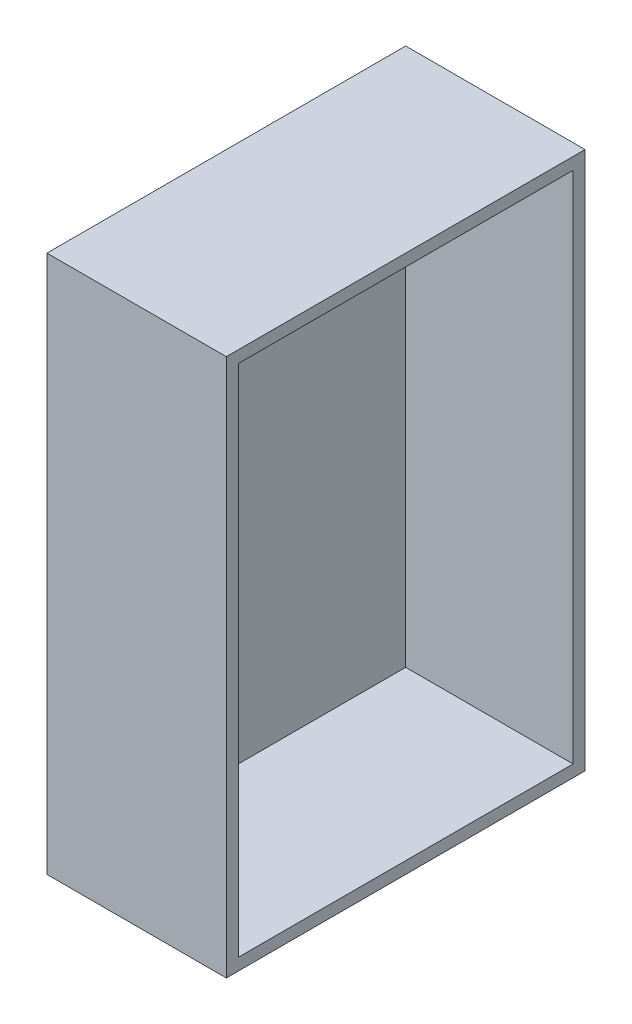
SolidWorks part; units mm, degrees
ref_plane "Front Plane" through (0, 0, 0) normal (1, 0, 0) x (0, 1, 0)
ref_plane "Top Plane" through (0, 0, 0) normal (0, 0, 1) x (0, 1, 0)
ref_plane "Right Plane" through (0, 0, 0) normal (0, 1, 0) x (-1, 0, 0)
sketch "Sketch1" plane through (0, 0, 0) normal (1, 0, 0) x (0, 1, 0)
  line L1 (45, -30) -> (-45, -30)
  line L2 (45, -30) -> (45, 30)
  line L3 (45, 30) -> (-45, 30)
  line L4 (-45, -30) -> (-45, 30)
  line L5 (45, -30) -> (-45, 30) construction
  line L6 (45, 30) -> (-45, -30) construction
  point P0 (0, 0)
  dimension "D1" = 90
  dimension "D2" = 60
extrude "Boss-Extrude1" add sketch "Sketch1" along normal blind 30
shell "Shell1" thickness 2 removed face at (30, 0, 0)
